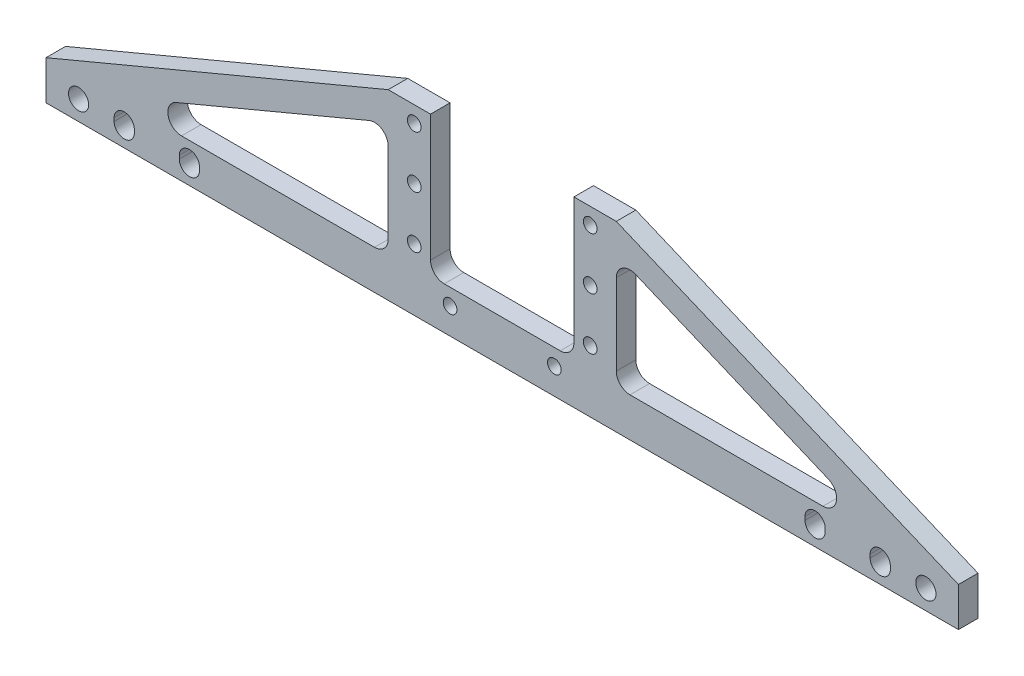
SolidWorks part; units mm, degrees
ref_plane "正面" through (0, 0, 0) normal (0, 0, 1) x (1, 0, 0)
ref_plane "平面" through (0, 0, 0) normal (0, 1, 0) x (1, 0, 0)
ref_plane "右側面" through (0, 0, 0) normal (1, 0, 0) x (0, 0, -1)
sketch "ｽｹｯﾁ1" plane through (0, 0, 0) normal (0, 0, 1) x (1, 0, 0)
  line L0 (-13.5, 21.5) -> (-13.5, 13.5) construction
  line L5 (-13.5, 13.5) -> (-13.5, 5.5) construction
  line L6 (-13.5, 5.5) -> (-13.5, 0) construction
  line L7 (-13.5, 0) -> (-8, 0) construction
  line L8 (-8, 0) -> (8, 0) construction
  line L9 (8, 0) -> (13.5, 0) construction
  line L10 (13.5, 0) -> (13.5, 5.5) construction
  line L11 (13.5, 5.5) -> (13.5, 13.5) construction
  line L12 (13.5, 13.5) -> (13.5, 21.5) construction
  line L13 (-11, 4.6) -> (-11, 24)
  line L14 (-11, 24) -> (-17.5, 24)
  line L15 (-17.5, 24) -> (-17.5, -4) construction
  line L16 (-17.5, -4) -> (17.5, -4)
  line L17 (17.5, -4) -> (17.5, 24) construction
  line L18 (17.5, 24) -> (11, 24)
  line L19 (11, 24) -> (11, 4.6)
  line L20 (8.9, 2.5) -> (-8.9, 2.5)
  line L21 (-17.5, 24) -> (-70, 2)
  line L22 (-70, -4) -> (-17.5, -4)
  line L23 (-17.5, 4.1) -> (-17.5, 16.5061)
  line L24 (-20.4116, 18.4429) -> (-50.017, 6.0368)
  line L25 (-49.2054, 2) -> (-19.6, 2)
  line L26 (-70, 2) -> (-70, -4)
  line L27 (-70, -1) -> (-65, -1) construction
  line L28 (-65, -1) -> (-65, -4) construction
  line L29 (0, -4) -> (0, 24) construction
  line L30 (70, -4) -> (17.5, -4)
  line L31 (70, 2) -> (70, -4)
  line L32 (17.5, 24) -> (70, 2)
  line L33 (20.4116, 18.4429) -> (50.017, 6.0368)
  line L34 (17.5, 4.1) -> (17.5, 16.5061)
  line L35 (49.2054, 2) -> (19.6, 2)
  circle A0 centre (-13.5, 5.5) radius 1.05
  circle A1 centre (-8, 0) radius 1.05
  circle A2 centre (8, 0) radius 1.05
  circle A3 centre (-13.5, 13.5) radius 1.05
  circle A4 centre (-13.5, 21.5) radius 1.05
  circle A5 centre (13.5, 21.5) radius 1.05
  circle A6 centre (13.5, 13.5) radius 1.05
  circle A7 centre (13.5, 5.5) radius 1.05
  arc A8 (-17.5, 4.1) -> (-19.6, 2) centre (-19.6, 4.1) cw
  arc A9 (-50.017, 6.0368) -> (-49.2054, 2) centre (-49.2054, 4.1) ccw
  arc A10 (-17.5, 16.5061) -> (-20.4116, 18.4429) centre (-19.6, 16.5061) ccw
  circle A11 centre (-65, -1) radius 1.55
  circle A12 centre (65, -1) radius 1.55
  arc A13 (17.5, 16.5061) -> (20.4116, 18.4429) centre (19.6, 16.5061) cw
  arc A14 (17.5, 4.1) -> (19.6, 2) centre (19.6, 4.1) ccw
  arc A15 (50.017, 6.0368) -> (49.2054, 2) centre (49.2054, 4.1) cw
  arc A16 (11, 4.6) -> (8.9, 2.5) centre (8.9, 4.6) cw
  arc A17 (-11, 4.6) -> (-8.9, 2.5) centre (-8.9, 4.6) ccw
  point P0 (0, 0)
  point P1 (0, 0)
  point P35 (-17.5, 2)
  point P40 (-17.5, 19.663)
  dimension "D3" = 2.1
  dimension "D15" = 2.1
  dimension "D17" = 3.1
  dimension "D19" = 2.1
  dimension "D1" = 5.5
  dimension "D2" = 8
  dimension "D4" = 27
  dimension "D5" = 2.5
  dimension "D6" = 2.5
  dimension "D7" = 2.5
  dimension "D8" = 4
  dimension "D9" = 4
  dimension "D10" = 2.5
  dimension "D11" = 4
  dimension "D12" = 70
  dimension "D13" = 4
  dimension "D14" = 6
  dimension "D16" = 6
  dimension "D18" = 5
extrude "ﾎﾞｽ - 押し出し1" add sketch "ｽｹｯﾁ1" along normal blind 3
sketch "ｽｹｯﾁ2" plane through (0, 0, 3) normal (0, 0, 1) x (1, 0, 0)
  line L0 (-70, -1) -> (-48, -1) construction
  line L1 (-70, 2) -> (-70, -4) construction
  line L2 (0, -4) -> (0, 2.5) construction
  line L3 (-70, -4) -> (70, -4) construction
  line L4 (8.9, 2.5) -> (-8.9, 2.5) construction
  circle A0 centre (-48, -1) radius 1.55
  circle A1 centre (48, -1) radius 1.55
  circle A2 centre (-58, -1) radius 1.55
  circle A3 centre (58, -1) radius 1.55
  dimension "D1" = 3.1
  dimension "D2" = 22
  dimension "D3" = 10
extrude "ｶｯﾄ - 押し出し1" cut sketch "ｽｹｯﾁ2" against normal blind 3
sketch "ｽｹｯﾁ3" plane through (0, 0, 0) normal (0, 0, -1) x (-1, 0, 0)
  line L0 (-58, -0.75) -> (-58, -1.25) construction
  line L1 (-56.45, -0.75) -> (-56.45, -1.25)
  line L2 (-59.55, -0.75) -> (-59.55, -1.25)
  line L3 (-48, -0.75) -> (-48, -1.25) construction
  line L4 (-46.45, -0.75) -> (-46.45, -1.25)
  line L5 (-49.55, -0.75) -> (-49.55, -1.25)
  line L6 (0, 2.5) -> (0, -4) construction
  line L7 (-8.9, 2.5) -> (8.9, 2.5) construction
  line L8 (70, -4) -> (-70, -4) construction
  line L9 (58, -0.75) -> (58, -1.25) construction
  line L10 (56.45, -0.75) -> (56.45, -1.25)
  line L11 (59.55, -0.75) -> (59.55, -1.25)
  line L12 (48, -0.75) -> (48, -1.25) construction
  line L13 (46.45, -0.75) -> (46.45, -1.25)
  line L14 (49.55, -0.75) -> (49.55, -1.25)
  arc A0 (-56.45, -0.75) -> (-59.55, -0.75) centre (-58, -0.75) ccw
  arc A1 (-59.55, -1.25) -> (-56.45, -1.25) centre (-58, -1.25) ccw
  circle A2 centre (-58, -1) radius 1.55 construction
  arc A3 (-46.45, -0.75) -> (-49.55, -0.75) centre (-48, -0.75) ccw
  arc A4 (-49.55, -1.25) -> (-46.45, -1.25) centre (-48, -1.25) ccw
  arc A5 (56.45, -0.75) -> (59.55, -0.75) centre (58, -0.75) cw
  arc A6 (59.55, -1.25) -> (56.45, -1.25) centre (58, -1.25) cw
  arc A7 (46.45, -0.75) -> (49.55, -0.75) centre (48, -0.75) cw
  arc A8 (49.55, -1.25) -> (46.45, -1.25) centre (48, -1.25) cw
  point P2 (-58, -1)
  point P13 (-48, -1)
  point P25 (58, -1)
  point P32 (48, -1)
  dimension "D1" = 0.5
  dimension "D2" = 2
extrude "ｶｯﾄ - 押し出し2" cut sketch "ｽｹｯﾁ3" against normal through all
